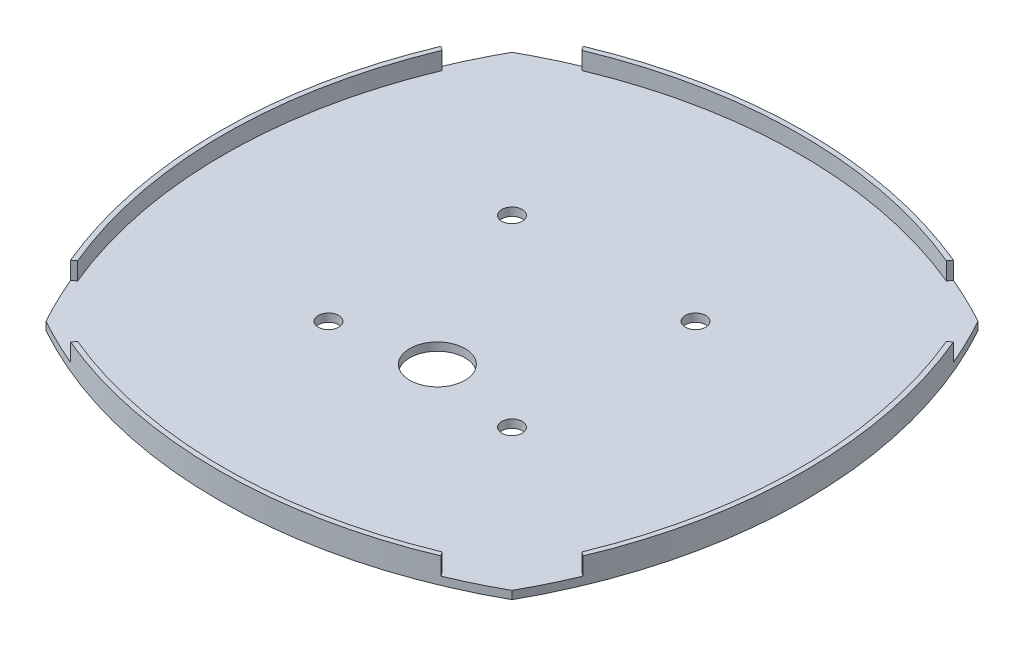
SolidWorks part; units mm, degrees
ref_plane "Front Plane" through (0, 0, 0) normal (0, 0, 1) x (1, 0, 0)
ref_plane "Top Plane" through (0, 0, 0) normal (0, 1, 0) x (1, 0, 0)
ref_plane "Right Plane" through (0, 0, 0) normal (1, 0, 0) x (0, 0, -1)
sketch "Sketch1" plane through (0, 0, 0) normal (0, 1, 0) x (1, 0, 0)
  line L0 (175.429, 389.4302) -> (225.429, 389.4742) construction
  dimension "D1" = 50
sketch "Sketch3" plane through (0, 0, 0) normal (0, 1, 0) x (1, 0, 0)
  line L2 (199.3319, -52.9004) -> (358.0133, -52.9004) construction
  line L3 (199.3319, -52.9004) -> (199.3319, 49.5555) construction
  arc A5 (130.4554, 15.9761) -> (130.4554, -121.7769) centre (256.8431, -52.9004) ccw construction
  arc A6 (268.2084, 15.9761) -> (130.4554, 15.9761) centre (199.3319, -110.4116) ccw construction
  arc A7 (268.2084, -121.7769) -> (268.2084, 15.9761) centre (141.8208, -52.9004) ccw construction
  arc A9 (130.4554, -121.7769) -> (268.2084, -121.7769) centre (199.3319, 4.6107) ccw construction
  arc A12 (271.1535, 18.9212) -> (127.5103, 18.9212) centre (199.3319, -110.4116) ccw
  arc A14 (127.5103, 18.9212) -> (127.5103, -124.722) centre (256.8431, -52.9004) ccw
  arc A15 (127.5103, -124.722) -> (271.1535, -124.722) centre (199.3319, 4.6107) ccw
  arc A16 (271.1535, -124.722) -> (271.1535, 18.9212) centre (141.8208, -52.9004) ccw
  point P0 (199.3319, -52.9004)
  point P15 (199.3319, -52.9004)
  dimension "D1" = 4
extrude "Boss-Extrude1" add sketch "Sketch3" along normal blind 2.5
sketch "Sketch5" plane through (0, 2.5, 0) normal (0, 1, 0) x (1, 0, 0)
  line L0 (141.8208, -52.9004) -> (256.8431, -52.9004) construction
  line L1 (199.3319, 4.6107) -> (199.3319, -110.4116) construction
  line L2 (121.6116, -109.0803) -> (120.3642, -109.9865)
  line L3 (143.1521, -130.6208) -> (142.2458, -131.8681)
  line L4 (277.0523, 3.2794) -> (278.2996, 4.1857)
  line L5 (255.5118, 24.8199) -> (256.418, 26.0673)
  line L6 (277.0523, -109.0803) -> (278.2996, -109.9865)
  line L7 (255.5118, -130.6208) -> (256.418, -131.8681)
  line L8 (121.6125, 3.2817) -> (120.3652, 4.1879)
  line L9 (143.1498, 24.819) -> (142.2436, 26.0663)
  line L10 (110.4063, 20.1528) -> (110.4063, -83.3423) construction
  line L11 (288.2576, 27.2093) -> (288.2576, -79.0531) construction
  line L12 (35.0838, 36.0252) -> (347.5932, 36.0252) construction
  line L13 (32.3242, -141.8261) -> (353.5329, -141.8261) construction
  arc A8 (128.614, -123.6184) -> (270.0499, -123.6184) centre (199.3319, 4.6107) ccw
  arc A9 (270.0499, -123.6184) -> (270.0499, 17.8175) centre (141.8208, -52.9004) ccw
  arc A10 (270.0499, 17.8175) -> (128.614, 17.8175) centre (199.3319, -110.4116) ccw
  arc A11 (128.614, 17.8175) -> (128.614, -123.6184) centre (256.8431, -52.9004) ccw
  arc A12 (143.1521, -130.6208) -> (255.5118, -130.6208) centre (199.3319, 4.6107) ccw
  arc A13 (277.0523, -109.0803) -> (277.0523, 3.2794) centre (141.8208, -52.9004) ccw
  arc A14 (255.5118, 24.8199) -> (143.1498, 24.819) centre (199.3319, -110.4116) ccw
  arc A15 (121.6125, 3.2817) -> (121.6116, -109.0803) centre (256.8431, -52.9004) ccw
  arc A21 (271.1535, 18.9212) -> (127.5103, 18.9212) centre (199.3319, -110.4116) ccw
  arc A22 (271.1535, -124.722) -> (271.1535, 18.9212) centre (141.8208, -52.9004) ccw
  arc A23 (127.5103, -124.722) -> (271.1535, -124.722) centre (199.3319, 4.6107) ccw
  arc A24 (127.5103, 18.9212) -> (127.5103, -124.722) centre (256.8431, -52.9004) ccw
  arc A25 (256.418, 26.0673) -> (142.2436, 26.0663) centre (199.3319, -110.4116) ccw
  arc A26 (278.2996, -109.9865) -> (278.2996, 4.1857) centre (141.8208, -52.9004) ccw
  arc A27 (142.2458, -131.8681) -> (256.418, -131.8681) centre (199.3319, 4.6107) ccw
  arc A28 (120.3652, 4.1879) -> (120.3642, -109.9865) centre (256.8431, -52.9004) ccw
  dimension "D2" = 36
  dimension "D3" = 36
  dimension "D4" = 36
  dimension "D5" = 36
  dimension "D6" = 36
  dimension "D7" = 36
  dimension "D8" = 36
  dimension "D9" = 36
  dimension "D1" = 1.5
  dimension "D10" = 0
extrude "Boss-Extrude2" add sketch "Sketch5" along normal blind 5.4
sketch "Sketch11" plane through (0, 2.5, 0) normal (0, 1, 0) x (1, 0, 0)
  line L0 (127.5103, -124.722) -> (271.1535, 18.9212) construction
  line L1 (127.5103, 18.9212) -> (271.1535, -124.722) construction
  line L2 (199.3319, -50.7415) -> (199.3319, 48.5237) construction
  line L3 (199.3319, -52.9004) -> (293.7423, -52.9004) construction
  circle A0 centre (171.0477, -24.6162) radius 3.15
  circle A1 centre (227.6162, -24.6162) radius 3.15
  circle A2 centre (227.6162, -81.1847) radius 3.15
  circle A3 centre (171.0477, -81.1847) radius 3.15
  circle A4 centre (199.3319, -75.9004) radius 8.5
  point P11 (199.3319, -52.9004)
  point P24 (199.3319, -52.9004)
  dimension "D2" = 6.3
  dimension "D4" = 17
  dimension "D3" = 40
  dimension "D5" = 23
  dimension "D1" = 4
extrude "Cut-Extrude2" cut sketch "Sketch11" against normal through all both and the other way through all
